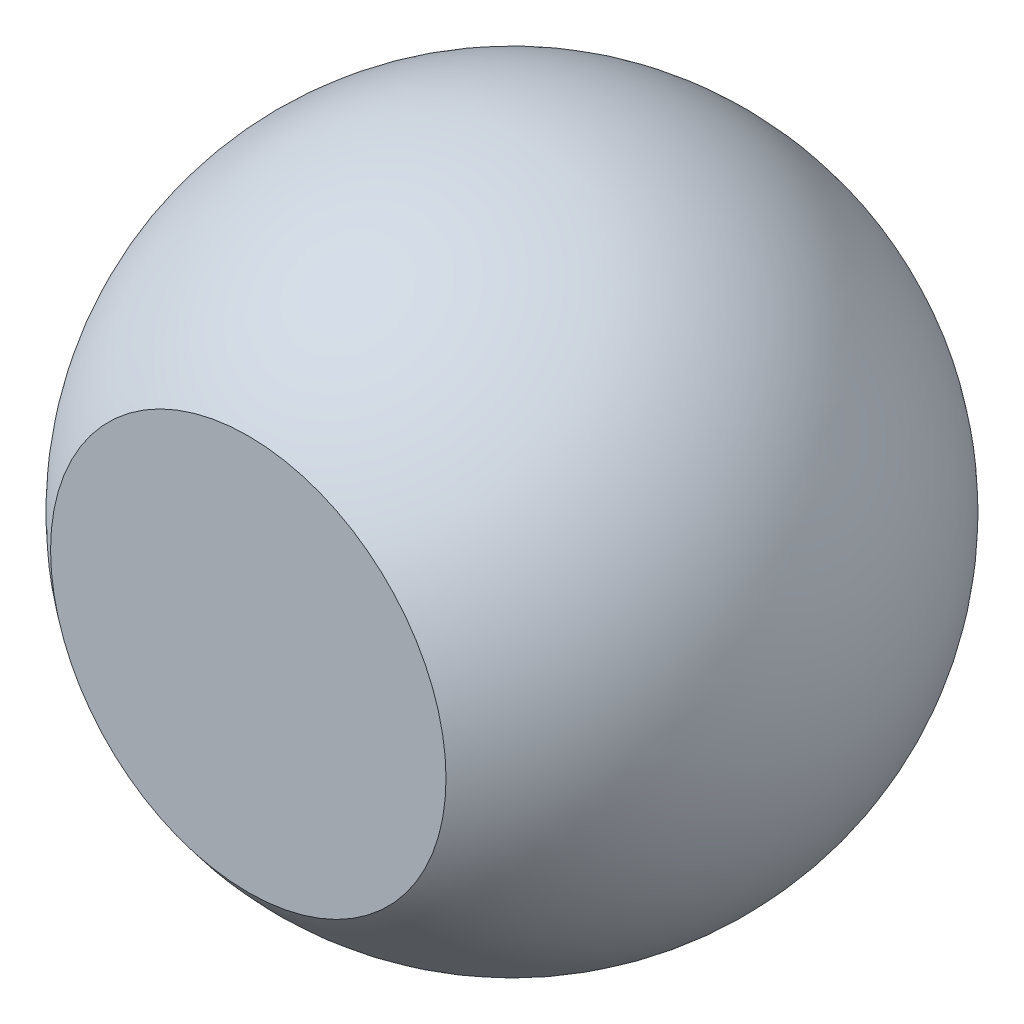
SolidWorks part; units mm, degrees
ref_plane "Front Plane" through (0, 0, 0) normal (0, 0, 1) x (1, 0, 0)
ref_plane "Top Plane" through (0, 0, 0) normal (0, 1, 0) x (1, 0, 0)
ref_plane "Right Plane" through (0, 0, 0) normal (1, 0, 0) x (0, 0, -1)
sketch "Sketch1" plane through (0, 0, 0) normal (0, 1, 0) x (1, 0, 0)
  line L0 (0, 0.2) -> (0, -0.2)
  line L1 (0, 0.2) -> (0.15, 0.2)
  line L2 (0, -0.2) -> (0.15, -0.2)
  arc A0 (0.15, -0.2) -> (0.15, 0.2) centre (0, 0) ccw
  dimension "D1" = 0.25
  dimension "D2" = 0.2
  dimension "D3" = 0.2
revolve "Revolve1" add sketch "Sketch1" angle 360 about L0
ref_axis "Axis1" through (0, 0, -0.22) along (0, 0, 1)
